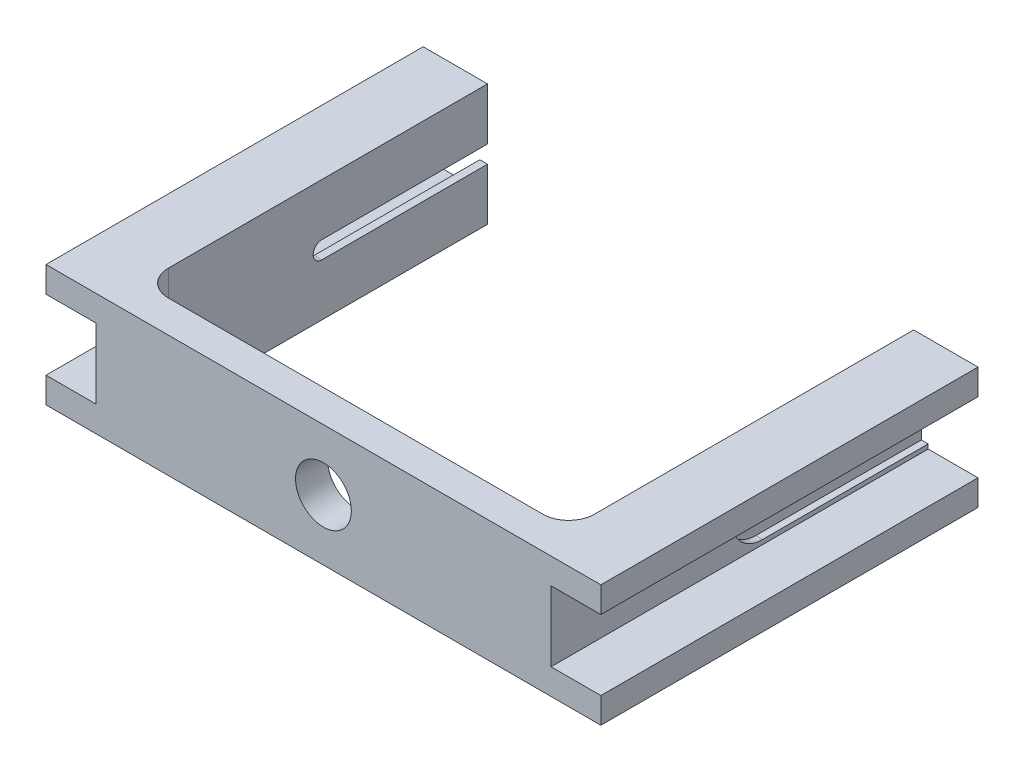
SolidWorks part; units mm, degrees
ref_plane "Front Plane" through (0, 0, 0) normal (0, 0, 1) x (1, 0, 0)
ref_plane "Top Plane" through (0, 0, 0) normal (0, 1, 0) x (1, 0, 0)
ref_plane "Right Plane" through (0, 0, 0) normal (1, 0, 0) x (0, 0, -1)
sketch "Sketch1" plane through (0, 0, 0) normal (0, 0, 1) x (1, 0, 0)
  line L1 (21.0219, -6) -> (-21.0219, -6)
  line L2 (21.0219, -6) -> (21.0219, 6)
  line L3 (21.0219, 6) -> (-21.0219, 6)
  line L4 (-21.0219, -6) -> (-21.0219, 6)
  line L5 (20.0219, -6) -> (-20.0219, -6) construction
  line L6 (-20.0219, 6) -> (20.0219, 6) construction
  line L9 (21.0219, 5.9218) -> (21.0219, -5.9218) construction
  line L10 (-21.0219, 5.9218) -> (-21.0219, -5.9218) construction
  circle A0 centre (0, 0) radius 2.5 construction
  circle A1 centre (0, 0) radius 2.5 construction
  circle A2 centre (0, 0) radius 2.754
  dimension "D1" = 0.254
extrude "Boss-Extrude1" add sketch "Sketch1" against normal blind 3.175
sketch "Sketch2" plane through (0, 0, 0) normal (0, 0, 1) x (1, 0, 0)
  line L0 (27.3719, 3.46) -> (27.3719, 6)
  line L1 (21.0219, -6) -> (27.3719, -6)
  line L2 (21.0219, -6) -> (21.0219, 6)
  line L3 (21.0219, 6) -> (27.3719, 6)
  line L4 (27.3719, -6) -> (27.3719, -3.46)
  line L5 (27.3719, -3.46) -> (22.4586, -3.46)
  line L7 (27.3719, 3.46) -> (22.4586, 3.46)
  line L8 (22.4586, -3.46) -> (22.4586, 3.46)
  dimension "D1" = 6.35
  dimension "D2" = 2.54
  dimension "D3" = 2.54
extrude "Boss-Extrude2" add sketch "Sketch2" against normal blind 37.211
ref_axis "Axis1" through (0, 0, -3.175) along (0, 0, 1)
ref_plane "Plane1" through (0, 0, 0) normal (1, 0, 0) x (0, 0, 1)
mirror "Mirror1" about plane through (0, 0, 0) normal (1, 0, 0) of "Boss-Extrude2"
sketch "Sketch3" plane through (22.4586, 0, 0) normal (1, 0, 0) x (0, 0, -1)
  line L0 (31.7719, 1.75) -> (20.8719, 1.75) construction
  line L1 (20.8719, -1.75) -> (31.7719, -1.75) construction
  line L2 (31.7719, 1.75) -> (20.8719, 1.75)
  line L3 (20.8719, -1.75) -> (31.7719, -1.75)
  arc A0 (20.8719, 1.75) -> (20.8719, -1.75) centre (20.8719, 0) ccw construction
  arc A1 (31.7719, -1.75) -> (31.7719, 1.75) centre (31.7719, 0) ccw construction
  arc A2 (20.8719, 1.75) -> (20.8719, -1.75) centre (20.8719, 0) ccw
  arc A3 (31.7719, -1.75) -> (31.7719, 1.75) centre (31.7719, 0) ccw
extrude "Cut-Extrude1" cut sketch "Sketch3" against normal through all
sketch "Sketch4" plane through (22.4586, 0, 0) normal (1, 0, 0) x (0, 0, -1)
  line L8 (31.7719, 3.02) -> (20.8719, 3.02)
  line L9 (20.8719, -3.02) -> (31.7719, -3.02)
  line L10 (31.7719, 3.02) -> (20.8719, 3.02)
  line L11 (20.8719, -3.02) -> (31.7719, -3.02)
  arc A6 (20.8719, 3.02) -> (20.8719, -3.02) centre (20.8719, 0) ccw
  arc A7 (31.7719, -3.02) -> (31.7719, 3.02) centre (31.7719, 0) ccw
  arc A8 (20.8719, 3.02) -> (20.8719, -3.02) centre (20.8719, 0) ccw
  arc A9 (31.7719, -3.02) -> (31.7719, 3.02) centre (31.7719, 0) ccw
  dimension "D1" = 1.27
extrude "Cut-Extrude2" cut sketch "Sketch4" against normal offset from surface (0.6746 mm away) 0.762 up to face at (21.0219, 0, -26.3219)
sketch "Sketch5" plane through (-22.4586, 0, 0) normal (-1, 0, 0) x (0, 0, 1)
  line L7 (-20.8719, 3.02) -> (-31.7719, 3.02)
  line L8 (-31.7719, -3.02) -> (-20.8719, -3.02)
  line L9 (-20.8719, 3.02) -> (-31.7719, 3.02)
  line L10 (-31.7719, -3.02) -> (-20.8719, -3.02)
  arc A7 (-20.8719, -3.02) -> (-20.8719, 3.02) centre (-20.8719, 0) ccw
  arc A8 (-31.7719, 3.02) -> (-31.7719, -3.02) centre (-31.7719, 0) ccw
  arc A9 (-20.8719, -3.02) -> (-20.8719, 3.02) centre (-20.8719, 0) ccw
  arc A10 (-31.7719, 3.02) -> (-31.7719, -3.02) centre (-31.7719, 0) ccw
  dimension "D1" = 1.27
extrude "Cut-Extrude3" cut sketch "Sketch5" against normal offset from surface (0.6746 mm away) 0.762 up to face at (-21.0219, 0, -26.3219)
fillet "Fillet1" radius 2.54 2 edges at (-21.0219, 0, -3.175) (21.0219, 0, -3.175)
sketch "Sketch6" plane through (0, 0, -37.211) normal (0, 0, -1) x (-1, 0, 0)
  line L0 (-21.7839, -3.02) -> (-22.4586, -3.02) construction
  line L1 (-21.0219, -1.75) -> (-21.7839, -1.75) construction
  line L2 (-21.0219, 1.75) -> (-21.7839, 1.75) construction
  line L3 (-21.7839, 3.02) -> (-22.4586, 3.02) construction
  line L4 (-21.7839, -3.02) -> (-22.4586, -3.02)
  line L5 (-21.0219, -1.75) -> (-21.7839, -1.75)
  line L6 (-21.0219, 1.75) -> (-21.7839, 1.75)
  line L7 (-21.7839, 3.02) -> (-22.4586, 3.02)
  line L8 (-21.7839, 3.02) -> (-21.7839, 1.75)
  line L9 (-22.4586, 3.02) -> (-22.4586, -3.02)
  line L10 (-21.0219, 1.75) -> (-21.0219, -1.75)
  line L11 (-21.7839, -1.75) -> (-21.7839, -3.02)
extrude "Cut-Extrude4" cut sketch "Sketch6" against normal blind 9.906
mirror "Mirror2" about plane through (0, 0, 0) normal (1, 0, 0) of "Cut-Extrude4"
sketch "Sketch8" plane through (-21.0219, 0, 0) normal (1, 0, 0) x (0, 0, -1)
  line L4 (37.211, -1.75) -> (20.8719, -1.75) construction
  line L5 (20.8719, 1.75) -> (37.211, 1.75) construction
  line L6 (20.8719, 0.861) -> (37.211, 0.861)
  line L7 (37.211, -0.861) -> (20.8719, -0.861)
  line L8 (20.8719, 0.861) -> (37.211, 0.861)
  line L9 (37.211, -0.861) -> (20.8719, -0.861)
  line L10 (37.211, -1.75) -> (20.8719, -1.75)
  line L11 (20.8719, 1.75) -> (37.211, 1.75)
  line L12 (37.211, 1.75) -> (37.211, 0.861)
  line L13 (37.211, -0.861) -> (37.211, -1.75)
  arc A2 (20.8719, 1.75) -> (20.8719, -1.75) centre (20.8719, 0) ccw construction
  arc A3 (20.8719, 0.861) -> (20.8719, -0.861) centre (20.8719, 0) ccw
  arc A4 (20.8719, 0.861) -> (20.8719, -0.861) centre (20.8719, 0) ccw
  arc A5 (20.8719, 1.75) -> (20.8719, -1.75) centre (20.8719, 0) ccw
  dimension "D1" = 0.889
extrude "Boss-Extrude3" add sketch "Sketch8" against normal up to surface (0.762 mm away) up to face at (-21.7839, 0, -28.4452)
sketch "Sketch9" plane through (21.0219, 0, 0) normal (-1, 0, 0) x (0, 0, 1)
  line L0 (-20.8719, -3.02) -> (-37.211, -3.02) construction
  line L1 (-37.211, 3.02) -> (-20.8719, 3.02) construction
  line L2 (-37.211, -3.02) -> (-37.211, -0.861) construction
  line L3 (-37.211, 0.861) -> (-37.211, 3.02) construction
  line L4 (-37.211, -0.861) -> (-20.8719, -0.861) construction
  line L5 (-20.8719, 0.861) -> (-37.211, 0.861) construction
  line L6 (-20.8719, -3.02) -> (-37.211, -3.02)
  line L7 (-37.211, 3.02) -> (-20.8719, 3.02)
  line L8 (-37.211, -3.02) -> (-37.211, -0.861)
  line L9 (-37.211, 0.861) -> (-37.211, 3.02)
  line L10 (-37.211, -0.861) -> (-20.8719, -0.861)
  line L11 (-20.8719, 0.861) -> (-37.211, 0.861)
  arc A0 (-20.8719, -3.02) -> (-20.8719, 3.02) centre (-20.8719, 0) ccw construction
  arc A1 (-20.8719, -0.861) -> (-20.8719, 0.861) centre (-20.8719, 0) ccw construction
  arc A2 (-20.8719, -3.02) -> (-20.8719, 3.02) centre (-20.8719, 0) ccw
  arc A3 (-20.8719, -0.861) -> (-20.8719, 0.861) centre (-20.8719, 0) ccw
extrude "Boss-Extrude4" add sketch "Sketch9" against normal up to surface (0.762 mm away) up to face at (21.7839, 0, -28.4452)
equation "\"D3@Sketch2\"=\"D2@Sketch2\""
